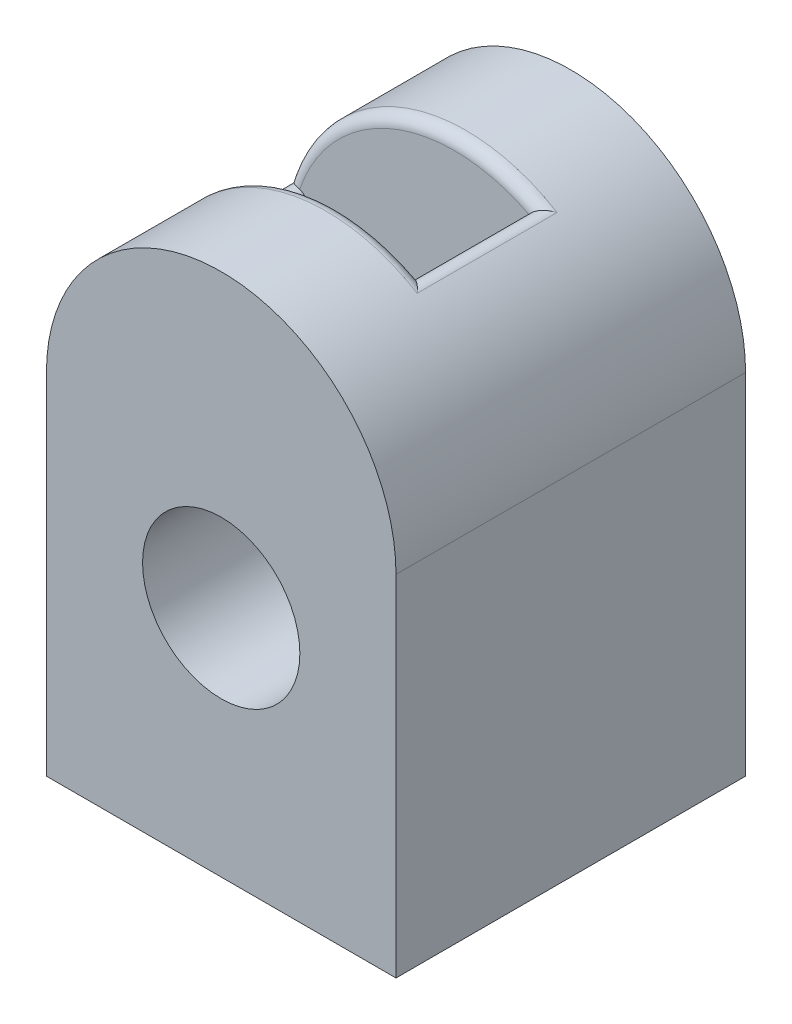
SolidWorks part; units mm, degrees
ref_plane "Front Plane" through (0, 0, 0) normal (0, 0, 1) x (1, 0, 0)
ref_plane "Top Plane" through (0, 0, 0) normal (0, 1, 0) x (1, 0, 0)
ref_plane "Right Plane" through (0, 0, 0) normal (1, 0, 0) x (0, 0, -1)
sketch "Sketch1" plane through (0, 0, 0) normal (0, 0, 1) x (1, 0, 0)
  line L1 (-15, -20) -> (15, -20)
  line L2 (-15, -20) -> (-15, 10)
  line L3 (-15, 10) -> (15, 10) construction
  line L4 (15, -20) -> (15, 10)
  line L5 (0, 10) -> (0, 0) construction
  line L6 (9.8481, 1.7365) -> (5.9642, 23.7633)
  line L7 (-13.1802, 17.1611) -> (-9.8481, -1.7365)
  circle A0 centre (0, 0) radius 6.75
  arc A1 (-15, 10) -> (15, 10) centre (0, 10) cw
  circle A2 centre (0, 0) radius 10
  point P2 (0, 0)
  point P3 (-13.53, 5.3531)
  point P4 (-14.2038, 14.822)
  dimension "D2" = 13.5
  dimension "D5" = 20
  dimension "D1" = 30
  dimension "D3" = 30
  dimension "D4" = 10
  dimension "D6" = 10
extrude "Boss-Extrude1" add sketch "Sketch1" along normal mid plane 30 contours A2 L7 L2 L1 L4 A1 L6 | A2 L6 A1 L7 | A2 A0 region at (-14.4694, -5, 0) region at (-2.4164, 15.4008, 0) region at (-1.6874, 9.5695, 0)
extrude "Cut-Extrude1" cut sketch "Sketch1<11>" against normal mid plane 10 contours A2 A0 | A2 L6 A1 L7 region at (-2.4164, 15.4008, 0) region at (-1.6874, 9.5695, 0)
sketch "Sketch1<11>" plane through (0, 0, 0) normal (0, 0, 1) x (1, 0, 0) same geometry as "Sketch1"
fillet "Fillet3" radius 1 4 edges at (-13.1802, 17.1611, 0) (-4.8903, 24.1804, -5) (5.9642, 23.7633, 0) (-4.8903, 24.1804, 5) type face fillet first side face at (0, 17.5, 0) second side face at (-11.5142, 7.7123, 0) second side face at (6.75, 0, 5) second side face at (7.9061, 12.7499, 0) second side face at (6.75, 0, -5)
